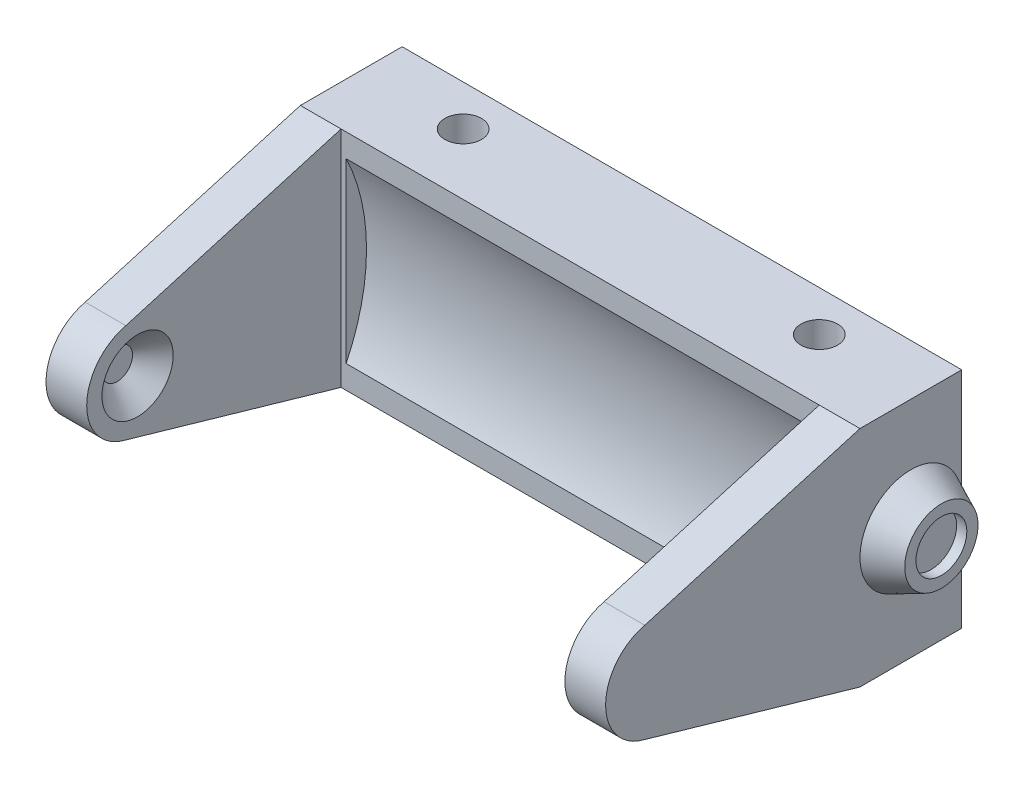
SolidWorks part; units mm, degrees
material "Oak"
ref_plane "Front Plane" through (0, 0, 0) normal (0, 0, 1) x (1, 0, 0)
ref_plane "Top Plane" through (0, 0, 0) normal (0, 1, 0) x (1, 0, 0)
ref_plane "Right Plane" through (0, 0, 0) normal (1, 0, 0) x (0, 0, -1)
sketch "Sketch1" plane through (0, 0, 0) normal (0, 0, 1) x (1, 0, 0)
  line L1 (-27.5, 11) -> (27.5, 11)
  line L2 (-27.5, 11) -> (-27.5, -11)
  line L3 (-27.5, -11) -> (27.5, -11)
  line L4 (27.5, 11) -> (27.5, -11)
  line L5 (-27.5, 11) -> (27.5, -11) construction
  line L6 (-27.5, -11) -> (27.5, 11) construction
  point P0 (0, 0)
  dimension "D1" = 22
  dimension "D2" = 55
extrude "Boss-Extrude1" add sketch "Sketch1" along normal blind 10
sketch "Sketch2" plane through (0, 0, 0) normal (0, 1, 0) x (1, 0, 0)
  line L0 (-17.5, -4) -> (17.5, -4) construction
  circle A0 centre (-17.5, -4) radius 1.8
  circle A1 centre (17.5, -4) radius 1.8
  point P4 (0, -4)
  dimension "D1" = 3.6
  dimension "D2" = 4
  dimension "D3" = 35
extrude "Cut-Extrude1" cut sketch "Sketch2" against normal through all both and the other way through all
sketch "Sketch3" plane through (0, 0, 0) normal (1, 0, 0) x (0, 0, -1)
  line L0 (-31.1511, 4.8351) -> (-10, 11)
  line L1 (-31.1677, -4.8923) -> (-10, -11)
  line L2 (-10, -11) -> (-10, 11)
  arc A0 (-31.1677, -4.8923) -> (-31.1511, 4.8351) centre (-30, -0.0306) cw
  dimension "D2" = 5
  dimension "D1" = 30
extrude "Boss-Extrude2" add sketch "Sketch3" along normal blind 4 from vertex starting at point (-27.5, 11, 10)
extrude "Boss-Extrude3" add sketch "Sketch3<2>" against normal blind 4 from vertex starting at point (27.5, 11, 10)
sketch "Sketch3<2>" plane through (0, 0, 0) normal (1, 0, 0) x (0, 0, -1) same geometry as "Sketch3"
sketch "Sketch4" plane through (0, 0, 0) normal (1, 0, 0) x (0, 0, -1)
  circle A0 centre (-30, 0) radius 3.5
  dimension "D1" = 7
  dimension "D2" = 30
extrude "Cut-Extrude2" cut sketch "Sketch4" against normal blind 2 draft 45 from surface starting at face at (-23.5, -0.0127, 21.5399)
extrude "Cut-Extrude3" cut sketch "Sketch4<2>" along normal blind 2 draft 45 from surface starting at face at (23.5, -0.0127, 21.5399)
sketch "Sketch4<2>" plane through (0, 0, 0) normal (1, 0, 0) x (0, 0, -1) same geometry as "Sketch4"
sketch "Sketch5" plane through (0, 0, 0) normal (1, 0, 0) x (0, 0, -1)
  line L0 (-20.6143, 18.5863) -> (-20.0581, -18.3555)
  arc A0 (-20.6143, 18.5863) -> (-20.0581, -18.3555) centre (-28, 0) cw
  dimension "D2" = 20
  dimension "D1" = 28
extrude "Cut-Extrude4" cut sketch "Sketch5" against normal mid plane 46
sketch "Sketch6" plane through (0, 0, 0) normal (1, 0, 0) x (0, 0, -1)
  circle A0 centre (-5, 0) radius 5
  dimension "D1" = 10
  dimension "D2" = 5
extrude "Boss-Extrude4" add sketch "Sketch6" along normal blind 3 draft 25 from surface starting at face at (27.5, -0.0085, 14.3599)
extrude "Boss-Extrude5" add sketch "Sketch6<2>" against normal blind 3 draft 25 from surface starting at face at (-27.5, -0.0085, 14.3599)
sketch "Sketch6<2>" plane through (0, 0, 0) normal (1, 0, 0) x (0, 0, -1) same geometry as "Sketch6"
sketch "Sketch7" plane through (0, 0, 0) normal (1, 0, 0) x (0, 0, -1)
  circle A0 centre (-5, 0) radius 2.5
  dimension "D1" = 5
extrude "Cut-Extrude5" cut sketch "Sketch7" against normal blind 1 from surface starting at face at (30.5, -3.6011, 5)
extrude "Cut-Extrude6" cut sketch "Sketch7<2>" along normal blind 1 from surface starting at face at (-30.5, 3.6011, 5)
sketch "Sketch7<2>" plane through (0, 0, 0) normal (1, 0, 0) x (0, 0, -1) same geometry as "Sketch7"
